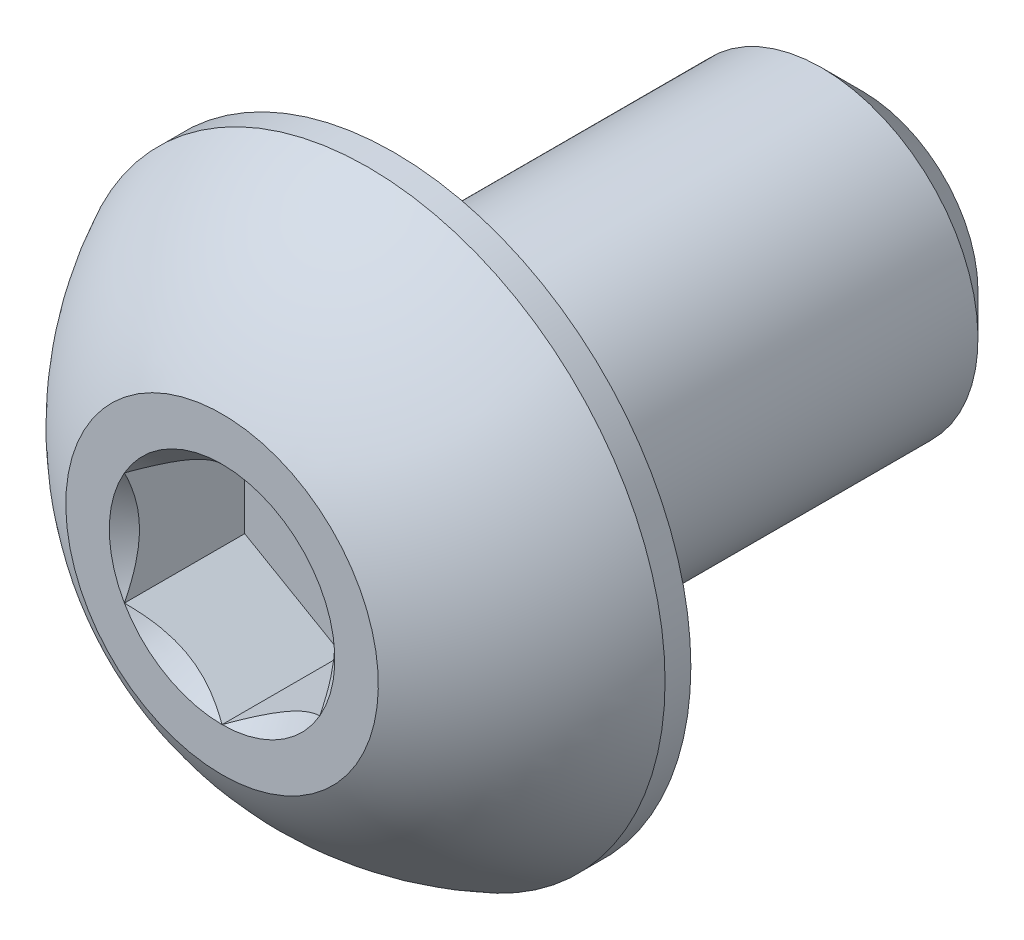
SolidWorks part; units mm, degrees
ref_plane "Front" through (0, 0, 0) normal (0, 0, 1) x (1, 0, 0)
ref_plane "Top" through (0, 0, 0) normal (0, 1, 0) x (1, 0, 0)
ref_plane "Right" through (0, 0, 0) normal (1, 0, 0) x (0, 0, -1)
sketch "Sketch1" plane through (0, 0, 0) normal (1, 0, 0) x (0, 0, -1)
  line L2 (2.2, 2) -> (8.2, 2)
  line L3 (8.2, 2) -> (8.2, 0)
  line L4 (8.2, 0) -> (2.2, 0)
  line L6 (1.87, 3.8) -> (2.2, 3.8) construction
  line L7 (8.2, 2) -> (8.2, -2) construction
  line L8 (0, 0) -> (2.2, 0) construction
  line L9 (2.2, 3.8) -> (2.2, -3.8) construction
  line L11 (2.2, 2) -> (2.2, 0)
  line L13 (0, 1.25) -> (0, -1.25) construction
  line L14 (0, 1.25) -> (0, 2) construction
  arc A3 (0, 2) -> (1.87, 3.8) centre (3.7264, 0) cw construction
  dimension "D1" = 0.33
revolve "Revolve1" add sketch "Sketch1" angle 360 mid plane about L4
sketch "Sketch3" plane through (0, 0, -8.2) normal (0, 0, -1) x (-1, 0, 0)
  circle A0 centre (0, 0) radius 2
curve "Helix/Spiral1" pitch 0.7 height 6.7 turns 9.5714
sketch "Sketch2" plane through (0, 0, 0) normal (1, 0, 0) x (0, 0, -1)
  line L0 (8.2, 2) -> (8.8125, 2)
  line L1 (8.8125, 2) -> (8.55, 1.5453)
  line L2 (8.55, 1.5453) -> (8.4625, 1.5453)
  line L3 (8.4625, 1.5453) -> (8.2, 2)
  line L4 (8.3312, 1.7727) -> (8.6812, 1.7727) construction
  dimension "D1" = 60
  dimension "D2" = 0.0875
  dimension "D3" = 0.35
chamfer "Chamfer1" distance 0.525 angle 45 1 edges at (0, 2, -8.2)
sweep "Cut-Sweep1" [suppressed] cut profiles "Sketch2" path "Helix/Spiral1"
sketch "Sketch7" plane through (0, 0, 0) normal (1, 0, 0) x (0, 0, -1)
  line L6 (1.87, 3.8) -> (2.2, 3.8) construction
  line L8 (0, 0) -> (2.2, 0) construction
  line L11 (2.2, 3.8) -> (2.2, -3.8) construction
  line L12 (1.87, 3.8) -> (2.2, 3.8)
  line L13 (0, 0) -> (2.2, 0)
  line L14 (0, 1.25) -> (0, -1.25) construction
  line L15 (2.2, 3.8) -> (2.2, 0)
  line L16 (0, 2) -> (0, 0)
  arc A2 (1.87, 3.8) -> (0, 2) centre (3.7264, 0) ccw construction
  arc A3 (1.87, 3.8) -> (0, 2) centre (3.7264, 0) ccw
revolve "Revolve2" add sketch "Sketch7" angle 360 mid plane about L13
sketch "Sketch5" plane through (0, 0, 0) normal (0, 0, 1) x (1, 0, 0)
  line L1 (1.25, -0.7217) -> (1.25, 0.7217)
  line L2 (1.25, 0.7217) -> (0, 1.4434)
  line L3 (0, 1.4434) -> (-1.25, 0.7217)
  line L4 (-1.25, 0.7217) -> (-1.25, -0.7217)
  line L5 (-1.25, -0.7217) -> (0, -1.4434)
  line L6 (0, -1.4434) -> (1.25, -0.7217)
  circle A0 centre (0, 0) radius 1.25 construction
extrude "Cut-Extrude2" cut sketch "Sketch5" against normal blind 1.54
sketch "Sketch6" plane through (0, 0, 0) normal (0, 0, 1) x (1, 0, 0)
  circle A0 centre (0, 0) radius 1.4434
extrude "Cut-Extrude3" cut sketch "Sketch6" against normal blind 1.54 draft 45
sketch "Sketch9" [suppressed] plane through (0, 0, -2.2) normal (0, 0, 1) x (1, 0, 0)
  circle A2 centre (0, 0) radius 2
extrude "Boss-Extrude2" [suppressed] add sketch "Sketch9" against normal offset from surface (5 mm away) 28.575
sketch "Sketch10" plane through (0, 0, 0) normal (1, 0, 0) x (0, 0, -1)
  line L0 (8.2, 2) -> (8.2, -2) construction
  point P0 (7.15, -2)
  dimension "D1" = 1.05
equation "\"D3@Helix/Spiral1\" = \"Lg@Sketch1\" + \"D4@Helix/Spiral1\""
equation "\"D2@Sketch2\" = \"D4@Helix/Spiral1\" * .125"
equation "\"D3@Sketch2\" = \"D4@Helix/Spiral1\" * .5"
equation "\"D1@Chamfer1\" = \"D4@Helix/Spiral1\" * .75"
equation "\"D1@Cut-Extrude2\" = \"Head Ht@Sketch1\" * .7"
equation "\"D1@Sketch1\" = \"Head Ht@Sketch1\" * .15"
equation "\"D1@Sketch10\" = \"D4@Helix/Spiral1\" * 1.5"
equation "\"D1@Cut-Extrude3\" = \"D1@Cut-Extrude2\""
